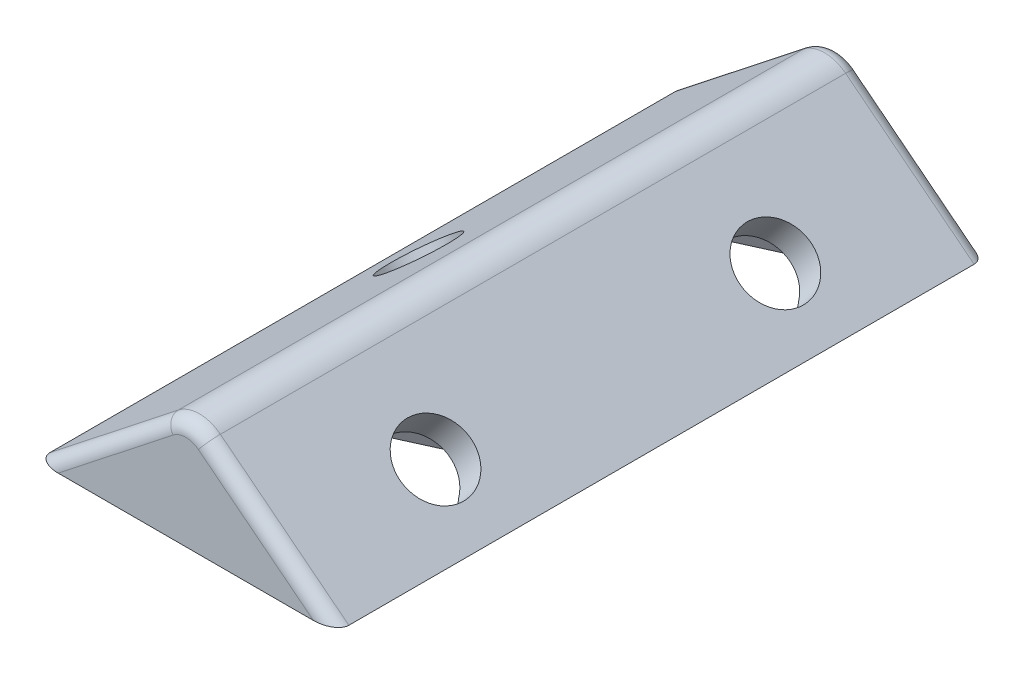
SolidWorks part; units mm, degrees
ref_plane "Front Plane" through (0, 0, 0) normal (0, 0, 1) x (1, 0, 0)
ref_plane "Top Plane" through (0, 0, 0) normal (0, 1, 0) x (1, 0, 0)
ref_plane "Right Plane" through (0, 0, 0) normal (1, 0, 0) x (0, 0, -1)
sketch "Sketch2" plane through (0, 0, 0) normal (0, 0, 1) x (1, 0, 0)
  line L1 (0, 2.3094) -> (-11, -6.3509)
  line L2 (-11, -6.3509) -> (11, -6.3509)
  line L3 (11, -6.3509) -> (0, 2.3094)
  dimension "D1" = 22
  dimension "D2" = 14
  dimension "D3" = 14
extrude "Boss-Extrude3" add sketch "Sketch2" along normal blind 48
sketch "Sketch4" plane through (-1.1224, 1.4257, 0) normal (-0.6186, 0.7857, 0) x (0.7857, 0.6186, 0)
  line L0 (-7.3214, -24) -> (1.4286, -24) construction
  line L1 (1.4286, -48) -> (1.4286, 0) construction
  circle A0 centre (-7.3214, -24) radius 2.625
  dimension "D1" = 5.25
  dimension "D2" = 8.75
extrude "Cut-Extrude2" cut sketch "Sketch4" against normal through all
sketch "Sketch5" plane through (1.1224, 1.4257, 0) normal (0.6186, 0.7857, 0) x (0.7857, -0.6186, 0)
  line L0 (7.3214, -36.5) -> (7.3214, -11.5) construction
  line L1 (-1.4286, -24) -> (7.3214, -24) construction
  line L2 (-1.4286, -48) -> (-1.4286, 0) construction
  circle A0 centre (7.3214, -11.5) radius 2.625
  circle A1 centre (7.3214, -36.5) radius 2.625
  dimension "D1" = 5.25
  dimension "D2" = 5.25
  dimension "D3" = 25
  dimension "D4" = 8.75
extrude "Cut-Extrude3" cut sketch "Sketch5" against normal through all
fillet "Fillet2" radius 2.5 1 edges at (0, 2.3094, 24)
ref_plane "Plane1" through (-8.1564, -10.36, 0) normal (0.6186, 0.7857, 0) x (0.7857, -0.6186, 0)
sketch "Sketch6" plane through (-8.1564, -10.36, 0) normal (0.6186, 0.7857, 0) x (0.7857, -0.6186, 0)
  line L1 (7.3214, -6.8235) -> (3.2714, -9.1617)
  line L2 (3.2714, -9.1617) -> (3.2714, -13.8383)
  line L3 (3.2714, -13.8383) -> (7.3214, -16.1765)
  line L4 (7.3214, -16.1765) -> (11.3714, -13.8383)
  line L5 (11.3714, -13.8383) -> (11.3714, -9.1617)
  line L6 (11.3714, -9.1617) -> (7.3214, -6.8235)
  line L7 (7.3214, -31.8235) -> (3.2714, -34.1617)
  line L8 (3.2714, -34.1617) -> (3.2714, -38.8383)
  line L9 (3.2714, -38.8383) -> (7.3214, -41.1765)
  line L10 (7.3214, -41.1765) -> (11.3714, -38.8383)
  line L11 (11.3714, -38.8383) -> (11.3714, -34.1617)
  line L12 (11.3714, -34.1617) -> (7.3214, -31.8235)
  circle A0 centre (7.3214, -11.5) radius 4.05 construction
  circle A1 centre (7.3214, -36.5) radius 4.05 construction
  dimension "D1" = 8.1
  dimension "D2" = 8.1
extrude "Cut-Extrude4" cut sketch "Sketch6" along normal blind 12.5
ref_plane "Plane2" through (8.1564, -10.36, 0) normal (-0.6186, 0.7857, 0) x (0.7857, 0.6186, 0)
sketch "Sketch7" plane through (8.1564, -10.36, 0) normal (-0.6186, 0.7857, 0) x (0.7857, 0.6186, 0)
  line L0 (-0.5397, -48) -> (-0.5397, 0) construction
  line L1 (-7.3214, -19.3235) -> (-11.3714, -21.6617)
  line L2 (-11.3714, -21.6617) -> (-11.3714, -26.3383)
  line L3 (-11.3714, -26.3383) -> (-7.3214, -28.6765)
  line L4 (-7.3214, -28.6765) -> (-3.2714, -26.3383)
  line L5 (-3.2714, -26.3383) -> (-3.2714, -21.6617)
  line L6 (-3.2714, -21.6617) -> (-7.3214, -19.3235)
  circle A0 centre (-7.3214, -24) radius 4.05 construction
  dimension "D1" = 8.1
extrude "Cut-Extrude6" cut sketch "Sketch7" along normal blind 12.5
fillet "Fillet3" radius 1 3 edges at (-6.2732, -2.6295, 0) (0, 1.6276, 0) (6.2732, -2.6295, 0)
fillet "Fillet4" radius 1 3 edges at (-6.2732, -2.6295, 48) (0, 1.6276, 48) (6.2732, -2.6295, 48)
